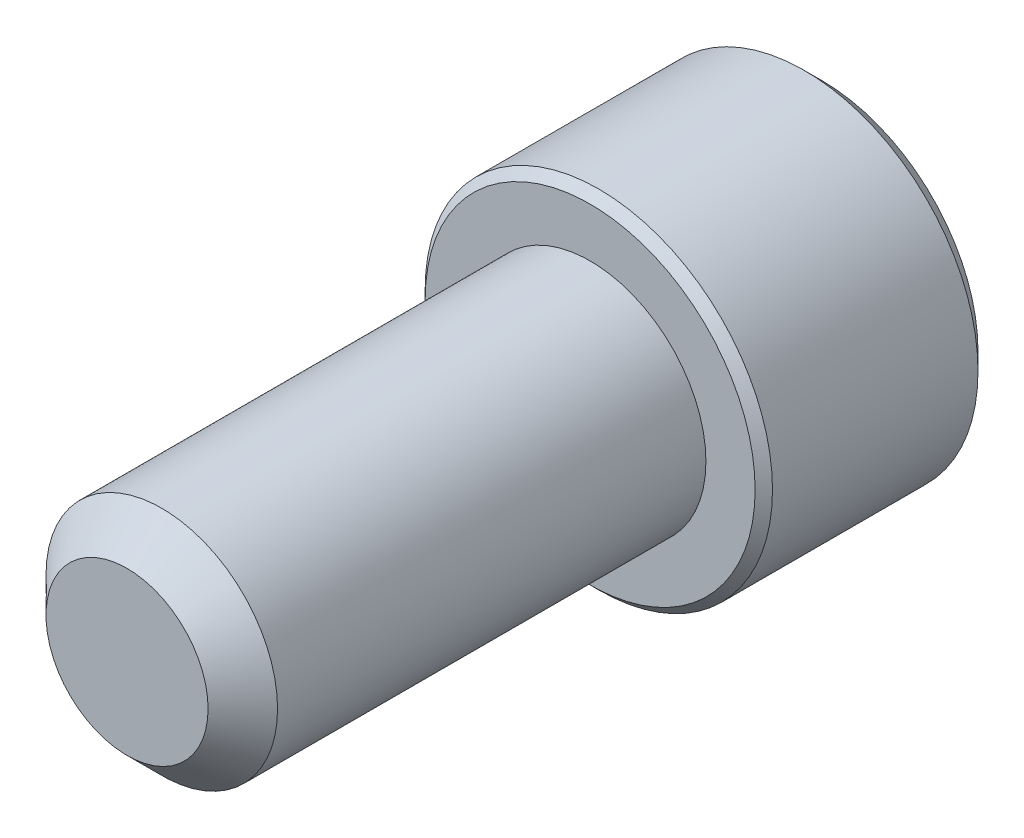
SolidWorks part; units mm, degrees
material "AISI 304"
ref_plane "Front Plane" through (0, 0, 0) normal (0, 0, 1) x (1, 0, 0)
ref_plane "Top Plane" through (0, 0, 0) normal (0, 1, 0) x (1, 0, 0)
ref_plane "Right Plane" through (0, 0, 0) normal (1, 0, 0) x (0, 0, -1)
sketch "Sketch0" plane through (0, 0, 0) normal (1, 0, 0) x (0, 0, -1)
  line L0 (0, 0) -> (12.7, 0) construction
  point P2 (19.05, 0)
  point P4 (0, 0)
  dimension "D1" = 12.7
  dimension "D2" = 6.35
  dimension "Min Thread" = 0
sketch "Sketch1" plane through (0, 0, 0) normal (0, 0, 1) x (1, 0, 0)
  circle A0 centre (0, 0) radius 3.175
  dimension "OD" = 6.35
extrude "Extrude1" add sketch "Sketch1" against normal blind 12.7
sketch "Sketch2" plane through (0, 0, 0) normal (0, 0, 1) x (1, 0, 0)
  circle A0 centre (0, 0) radius 3.175 construction
  circle A1 centre (0, 0) radius 3.175
curve "Helix/Spiral1" pitch 1.27 height 13.97 turns 11 parameters "pitch"=1.27
chamfer "Chamfer3" distance 0.9525 angle 45 1 edges at (3.175, 0, 0)
sketch "Sketch3" plane through (0, 0, 0) normal (1, 0, 0) x (0, 0, -1)
  line L0 (-1.1113, 3.175) -> (-0.635, 2.3501)
  line L1 (-0.635, 2.3501) -> (-0.4763, 2.3501)
  line L2 (-0.4763, 2.3501) -> (0, 3.175)
  line L3 (-1.1113, 3.175) -> (0, 3.175)
  line L4 (-0.5556, 3.175) -> (-0.5556, 2.3501) construction
  line L5 (-0.8731, 2.7626) -> (-0.2381, 2.7626) construction
  line L6 (0, 3.175) -> (0, -3.175) construction
  dimension "D1" = 0.1588
  dimension "D2" = 0.635
  dimension "D3" = 60
sweep "Cut-Sweep1" [suppressed] cut profiles "Sketch3" path "Helix/Spiral1"
sketch "Sketch5" [suppressed] plane through (0, 0, 0) normal (1, 0, 0) x (0, 0, -1)
  line L0 (12.7, -2.3728) -> (12.7, 2.2654) construction
  line L1 (12.7, 3.175) -> (0, 3.175)
  line L2 (12.7, 3.175) -> (12.7, 0)
  line L3 (12.7, 0) -> (-1.1556, 0)
  line L4 (0, 0) -> (12.7, 0) construction
  line L5 (0, 3.175) -> (-1.1556, 0)
  line L6 (0, 0) -> (15.24, 0) construction
  dimension "D1" = 70
  dimension "D3" = 2.54
revolve "partially thread" [suppressed] add sketch "Sketch5" angle 360 about L6
sketch "Sketch6" plane through (0, 0, -12.7) normal (0, 0, -1) x (-1, 0, 0)
  circle A0 centre (0, 0) radius 4.7625
  dimension "head dia" = 9.525
extrude "Extrude2" add sketch "Sketch6" along normal blind 6.35
sketch "Sketch7" plane through (0, 0, -19.05) normal (0, 0, -1) x (-1, 0, 0)
  line L1 (0, 2.7496) -> (-2.3813, 1.3748)
  line L2 (-2.3813, 1.3748) -> (-2.3813, -1.3748)
  line L3 (-2.3813, -1.3748) -> (0, -2.7496)
  line L4 (0, -2.7496) -> (2.3813, -1.3748)
  line L5 (2.3813, -1.3748) -> (2.3813, 1.3748)
  line L6 (2.3813, 1.3748) -> (0, 2.7496)
  circle A0 centre (0, 0) radius 2.3813 construction
  dimension "hex dia" = 4.7625
extrude "Cut-Extrude1" cut sketch "Sketch7" against normal blind 3.5719
sketch "Sketch8" plane through (0, 0, -19.05) normal (0, 0, -1) x (-1, 0, 0)
  circle A0 centre (0, 0) radius 2.7496
extrude "Cut-Extrude2" [suppressed] cut sketch "Sketch8" against normal through all draft 45
chamfer "Chamfer1" distance 0.4763 angle 45 1 edges at (-4.7625, 0, -19.05)
chamfer "Chamfer2" distance 0.2381 angle 45 1 edges at (-4.7625, 0, -12.7)
sketch "Sketch9" plane through (0, 0, 0) normal (1, 0, 0) x (0, 0, -1)
  line L0 (0, 3.175) -> (0, -3.175) construction
  line L1 (3.175, 3.175) -> (3.175, -3.175) construction
  line L2 (19.05, 4.7625) -> (19.05, -4.7625) construction
  line L3 (12.7, 4.7625) -> (12.7, -4.7625) construction
  line L4 (12.7, 4.5244) -> (12.7, -4.5244) construction
  line L5 (19.05, -4.2863) -> (19.05, 4.2863) construction
  line L6 (12.7, -4.7625) -> (12.7, 4.7625) construction
  line L7 (0, 2.2225) -> (0, -2.2225) construction
  line L8 (-1.1113, 3.175) -> (0, 3.175) construction
  line L9 (3.175, 0) -> (0, 0) construction
  dimension "D1" = 3.175
equation "\"D3@Helix/Spiral1\" = \"screw length@Extrude1\"+\"pitch@Helix/Spiral1\""
equation "\"D1@Sketch3\" = \"pitch@Helix/Spiral1\"*.125"
equation "\"D2@Sketch3\" = \"pitch@Helix/Spiral1\"*.5"
equation "\"D1@Cut-Extrude1\" = \"hex dia@Sketch7\"*.75"
equation "\"D1@Chamfer1\" = \"head dia@Sketch6\"*.05"
equation "\"D1@Sketch9\" = \"pitch@Helix/Spiral1\"*2.50"
equation "\"D1@Chamfer2\" = \"D1@Chamfer1\"/2"
equation "\"D1@Chamfer3\" = \"pitch@Helix/Spiral1\"*.750"
equation "\"D1@Sketch0\" = \"screw length@Extrude1\""
equation "\"D2@Sketch0\" = \"head depth@Extrude2\""
